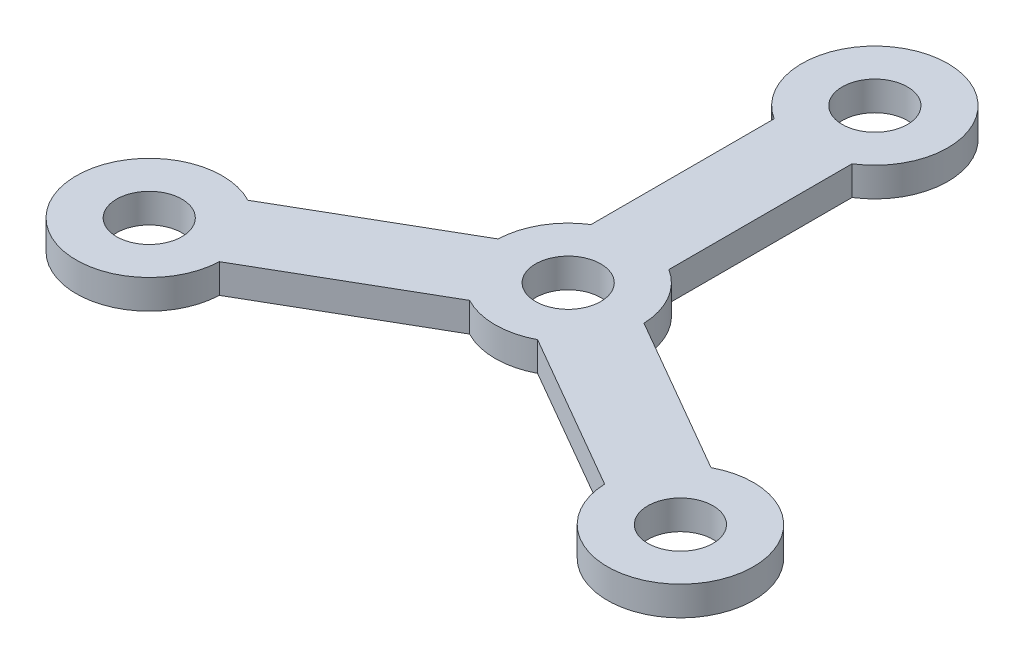
SolidWorks part; units mm, degrees
ref_plane "Front Plane" through (0, 0, 0) normal (0, 0, 1) x (1, 0, 0)
ref_plane "Top Plane" through (0, 0, 0) normal (0, 1, 0) x (1, 0, 0)
ref_plane "Right Plane" through (0, 0, 0) normal (1, 0, 0) x (0, 0, -1)
sketch "Sketch1" plane through (0, 0, 0) normal (0, 1, 0) x (1, 0, 0)
  line L0 (0, 31.5) -> (0, 0) construction
  line L1 (-4, 25.1557) -> (-4, 6.3443)
  line L2 (4, 25.1557) -> (4, 6.3443)
  line L3 (23.7855, -9.1138) -> (7.4943, 0.292)
  line L4 (19.7855, -16.042) -> (3.4943, -6.6362)
  line L5 (-19.7855, -16.042) -> (-3.4943, -6.6362)
  line L6 (-23.7855, -9.1138) -> (-7.4943, 0.292)
  circle A0 centre (0, 0) radius 31.5
  circle A1 centre (0, 0) radius 3.35
  circle A2 centre (0, 0) radius 7.5
  circle A3 centre (0, 31.5) radius 7.5
  circle A4 centre (0, 31.5) radius 3.35
  circle A5 centre (27.2798, -15.75) radius 7.5
  circle A6 centre (27.2798, -15.75) radius 3.35
  circle A7 centre (-27.2798, -15.75) radius 7.5
  circle A8 centre (-27.2798, -15.75) radius 3.35
  point P29 (0, 0)
  dimension "D1" = 63
  dimension "D2" = 6.7
  dimension "D3" = 15
  dimension "D4" = 6.7
  dimension "D5" = 15
  dimension "D6" = 4
extrude "Boss-Extrude1" add sketch "Sketch1" along normal blind 3 contours A7 L5 A2 L6 | A8 A0 A7 | A8 A0 A7 | A6 A0 A5 | A6 A0 A5 | A5 L3 A2 L4 | A3 L0 A2 L2 | A4 L0 A3 A0 | L0 A4 A0 A3 | A4 A0 A3 | L0 A3 L1 A2 | A2 A1 region at (3.4817, 0, -27.6743) region at (-3.4817, 0, -27.6743) region at (0, 0, -34.9091) region at (2.0439, 0, -15.75) region at (-2.0439, 0, -15.75) region at (2.0229, 0, -7.0015) region at (-23.9666, 0, 13.8371) region at (-30.2322, 0, 17.4546) region at (30.2322, 0, 17.4546) region at (23.9666, 0, 13.8371) region at (-13.6399, 0, 7.875) region at (13.6399, 0, 7.875)
